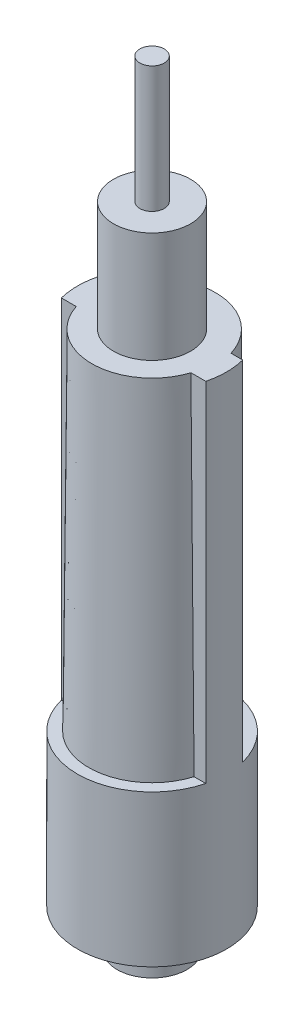
SolidWorks part; units mm, degrees
ref_plane "Front" through (0, 0, 0) normal (0, 0, 1) x (1, 0, 0)
ref_plane "Top" through (0, 0, 0) normal (0, 1, 0) x (1, 0, 0)
ref_plane "Right" through (0, 0, 0) normal (1, 0, 0) x (0, 0, -1)
sketch "Sketch2" plane through (0, 0, 0) normal (0, 0, 1) x (1, 0, 0)
  line L0 (0, 0) -> (0, 168.402)
  line L1 (0, -50) -> (0, 50) construction
  line L2 (0, 168.402) -> (10.033, 168.402)
  line L3 (10.033, 168.402) -> (10.033, 139.7)
  line L4 (10.033, 139.7) -> (16.4465, 139.7)
  line L5 (16.4465, 139.7) -> (16.4465, 49.149)
  line L6 (16.4465, 49.149) -> (19.3802, 49.149)
  line L7 (19.3802, 49.149) -> (19.3802, 9.7536)
  line L8 (50, 0) -> (-50, 0) construction
  line L9 (9.1059, 0) -> (0, 0)
  line L10 (19.3802, 9.7536) -> (9.1059, 9.7536)
  line L11 (9.1059, 9.7536) -> (9.1059, 0)
  dimension "D1" = 9.1059
  dimension "D2" = 16.4465
  dimension "D3" = 10.033
  dimension "D4" = 28.702
  dimension "D5" = 90.551
  dimension "D6" = 39.3954
  dimension "D7" = 9.7536
  dimension "D8" = 19.3802
revolve "Revolve1" add sketch "Sketch2" angle 360 about L0
sketch "Sketch3" plane through (0, 49.149, 0) normal (0, 1, 0) x (1, 0, 0)
  line L1 (-18.7762, -4.8006) -> (18.7762, -4.8006)
  line L2 (-18.7762, -4.8006) -> (-18.7762, 4.8006) construction
  line L3 (-18.7762, 4.8006) -> (18.7762, 4.8006)
  line L4 (18.7762, -4.8006) -> (18.7762, 4.8006) construction
  line L5 (-18.7762, -4.8006) -> (18.7762, 4.8006) construction
  line L6 (-18.7762, 4.8006) -> (18.7762, -4.8006) construction
  arc A1 (-18.7762, 4.8006) -> (-18.7762, -4.8006) centre (0, 0) ccw
  arc A2 (18.7762, 4.8006) -> (18.7762, -4.8006) centre (0, 0) cw
  circle A3 centre (0, 0) radius 19.3802 construction
  point P0 (0, 0)
  dimension "D1" = 9.6012
extrude "Boss-Extrude1" add sketch "Sketch3" along normal up to surface (90.551 mm away) up to face at (0, 139.7, -10.033)
draft "Draft1" type of draft neutral plane draft angle 0.5 faces to draft 1 face at (0, 94.4245, 10.6235) neutral plane through (16.4465, 49.149, 0) neutral plane normal (0, 1, 0) parameters "D1"=0.5
sketch "Sketch4" plane through (0, 168.402, 0) normal (0, 1, 0) x (1, 0, 0)
  circle A0 centre (0, 0) radius 3.175
  dimension "D1" = 6.35
extrude "Boss-Extrude2" add sketch "Sketch4" along normal blind 32.766
